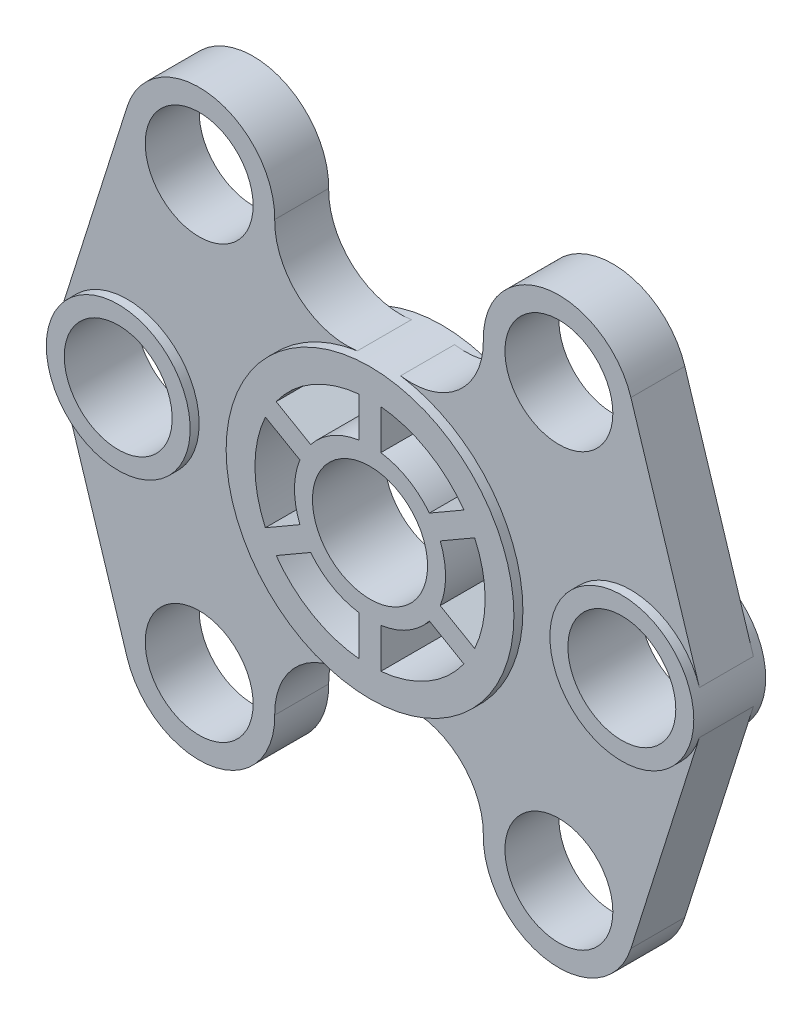
SolidWorks part; units mm, degrees
ref_plane "Front Plane" through (0, 0, 0) normal (0, 0, 1) x (1, 0, 0)
ref_plane "Top Plane" through (0, 0, 0) normal (0, 1, 0) x (1, 0, 0)
ref_plane "Right Plane" through (0, 0, 0) normal (1, 0, 0) x (0, 0, -1)
sketch "Sketch1" plane through (0, 0, 0) normal (0, 0, 1) x (1, 0, 0)
  line L0 (0, -1064) -> (0, -40) construction
  line L1 (0, 0) -> (-29571.221, 0) construction
  line L2 (-3, -20.7846) -> (-3, -31.8591)
  line L3 (3, -20.7846) -> (3, -31.8591)
  line L4 (-19.5, -7.7942) -> (-29.0908, -13.3315)
  line L5 (-16.5, -12.9904) -> (-26.0908, -18.5276)
  line L6 (-16.5, 12.9904) -> (-26.0908, 18.5276)
  line L7 (-19.5, 7.7942) -> (-29.0908, 13.3315)
  line L8 (3, 20.7846) -> (3, 31.8591)
  line L9 (-3, 20.7846) -> (-3, 31.8591)
  line L10 (19.5, 7.7942) -> (29.0908, 13.3315)
  line L11 (16.5, 12.9904) -> (26.0908, 18.5276)
  line L12 (16.5, -12.9904) -> (26.0908, -18.5276)
  line L13 (19.5, -7.7942) -> (29.0908, -13.3315)
  line L14 (0, 21) -> (0, 29571.221) construction
  line L15 (0, -21) -> (0, 16) construction
  line L16 (70.0249, 66.325) -> (89.0713, 6.0238)
  line L17 (70.0249, -66.325) -> (89.0713, -6.0238)
  line L18 (-70.0249, 66.325) -> (-89.0713, 6.0238)
  line L19 (-70.0249, -66.325) -> (-89.0713, -6.0238)
  circle A0 centre (0, 0) radius 16
  arc A1 (-3, 20.7846) -> (-16.5, 12.9904) centre (0, 0) ccw
  arc A2 (-29.0908, 13.3315) -> (-29.0908, -13.3315) centre (0, 0) ccw
  circle A3 centre (0, 0) radius 40
  arc A4 (-29.0908, 13.3315) -> (-29.0908, -13.3315) centre (0, 0) ccw
  arc A5 (-29.0908, 13.3315) -> (-29.0908, -13.3315) centre (0, 0) ccw
  arc A6 (-29.0908, 13.3315) -> (-29.0908, -13.3315) centre (0, 0) ccw
  arc A7 (-29.0908, 13.3315) -> (-29.0908, -13.3315) centre (0, 0) ccw
  arc A8 (-29.0908, 13.3315) -> (-29.0908, -13.3315) centre (0, 0) ccw
  arc A9 (-3, 31.8591) -> (-26.0908, 18.5276) centre (0, 0) ccw
  arc A10 (-3, 31.8591) -> (-26.0908, 18.5276) centre (0, 0) ccw
  arc A11 (-3, 31.8591) -> (-26.0908, 18.5276) centre (0, 0) ccw
  arc A12 (-3, 31.8591) -> (-26.0908, 18.5276) centre (0, 0) ccw
  arc A13 (-3, 31.8591) -> (-26.0908, 18.5276) centre (0, 0) ccw
  arc A14 (-3, 31.8591) -> (-26.0908, 18.5276) centre (0, 0) ccw
  arc A15 (-19.5, 7.7942) -> (-19.5, -7.7942) centre (0, 0) ccw
  arc A16 (-16.5, -12.9904) -> (-3, -20.7846) centre (0, 0) ccw
  arc A17 (-26.0908, -18.5276) -> (-3, -31.8591) centre (0, 0) ccw
  arc A18 (-26.0908, -18.5276) -> (-3, -31.8591) centre (0, 0) ccw
  arc A19 (-26.0908, -18.5276) -> (-3, -31.8591) centre (0, 0) ccw
  arc A20 (-26.0908, -18.5276) -> (-3, -31.8591) centre (0, 0) ccw
  arc A21 (-26.0908, -18.5276) -> (-3, -31.8591) centre (0, 0) ccw
  arc A22 (-26.0908, -18.5276) -> (-3, -31.8591) centre (0, 0) ccw
  arc A23 (3, -20.7846) -> (16.5, -12.9904) centre (0, 0) ccw
  arc A24 (3, -31.8591) -> (26.0908, -18.5276) centre (0, 0) ccw
  arc A25 (3, -31.8591) -> (26.0908, -18.5276) centre (0, 0) ccw
  arc A26 (3, -31.8591) -> (26.0908, -18.5276) centre (0, 0) ccw
  arc A27 (3, -31.8591) -> (26.0908, -18.5276) centre (0, 0) ccw
  arc A28 (3, -31.8591) -> (26.0908, -18.5276) centre (0, 0) ccw
  arc A29 (3, -31.8591) -> (26.0908, -18.5276) centre (0, 0) ccw
  arc A30 (19.5, -7.7942) -> (19.5, 7.7942) centre (0, 0) ccw
  arc A31 (29.0908, -13.3315) -> (29.0908, 13.3315) centre (0, 0) ccw
  arc A32 (29.0908, -13.3315) -> (29.0908, 13.3315) centre (0, 0) ccw
  arc A33 (29.0908, -13.3315) -> (29.0908, 13.3315) centre (0, 0) ccw
  arc A34 (29.0908, -13.3315) -> (29.0908, 13.3315) centre (0, 0) ccw
  arc A35 (29.0908, -13.3315) -> (29.0908, 13.3315) centre (0, 0) ccw
  arc A36 (29.0908, -13.3315) -> (29.0908, 13.3315) centre (0, 0) ccw
  arc A37 (16.5, 12.9904) -> (3, 20.7846) centre (0, 0) ccw
  arc A38 (26.0908, 18.5276) -> (3, 31.8591) centre (0, 0) ccw
  arc A39 (26.0908, 18.5276) -> (3, 31.8591) centre (0, 0) ccw
  arc A40 (26.0908, 18.5276) -> (3, 31.8591) centre (0, 0) ccw
  arc A41 (26.0908, 18.5276) -> (3, 31.8591) centre (0, 0) ccw
  arc A42 (26.0908, 18.5276) -> (3, 31.8591) centre (0, 0) ccw
  arc A43 (26.0908, 18.5276) -> (3, 31.8591) centre (0, 0) ccw
  arc A44 (70.0249, 66.325) -> (29.0029, 59.6519) centre (50, 60) ccw
  circle A45 centre (50, 60) radius 15
  circle A46 centre (50, -60) radius 15
  arc A47 (70.0249, -66.325) -> (29.0029, -59.6519) centre (50, -60) cw
  circle A48 centre (70, 0) radius 20
  circle A49 centre (70, 0) radius 15
  arc A50 (6.0038, 39.5469) -> (29.0029, 59.6519) centre (9.0056, 59.3203) ccw
  arc A51 (6.0038, -39.5469) -> (29.0029, -59.6519) centre (9.0056, -59.3203) cw
  arc A52 (-6.0038, -39.5469) -> (-29.0029, -59.6519) centre (-9.0056, -59.3203) ccw
  circle A53 centre (-50, -60) radius 15
  arc A54 (-70.0249, -66.325) -> (-29.0029, -59.6519) centre (-50, -60) ccw
  circle A55 centre (-70, 0) radius 15
  circle A56 centre (-70, 0) radius 20
  circle A57 centre (-50, 60) radius 15
  arc A58 (-70.0249, 66.325) -> (-29.0029, 59.6519) centre (-50, 60) cw
  arc A59 (-6.0038, 39.5469) -> (-29.0029, 59.6519) centre (-9.0056, 59.3203) cw
  point P41 (0, 0)
  point P50 (79.5481, 36.1744)
  dimension "D1" = 32
  dimension "D2" = 42
  dimension "D3" = 64
  dimension "D4" = 80
  dimension "D7" = 50
  dimension "D9" = 42
  dimension "D10" = 30
  dimension "D11" = 30
  dimension "D12" = 40
  dimension "D15" = 20
  dimension "D5" = 6
  dimension "D6" = 6
  dimension "D8" = 60
  dimension "D13" = 20
  dimension "D14" = 120
  dimension "D16" = 21
extrude "Boss-Extrude2" add sketch "Sketch1" along normal mid plane 20 contours A3 A38 L11 A37 L8 A31 L13 A30 L10 A24 L3 A23 L12 A17 L5 A16 L2 A9 L9 A1 L6 A0 L7 A15 L4 A2 | A49 | A48 | A56 | A55 region at (29.4748, 25.3378, 0)
extrude "Boss-Extrude3" add sketch "Sketch1<4>" along normal mid plane 15 contours A3 A51 A47 L17 A48 L16 A44 A50 A46 A45 | A3 A59 A58 L18 A56 L19 A54 A52 A57 A53 region at (77.8121, 35.626, 0) region at (-41.8206, 0, 0)
sketch "Sketch1<4>" plane through (0, 0, 0) normal (0, 0, 1) x (1, 0, 0) same geometry as "Sketch1"
